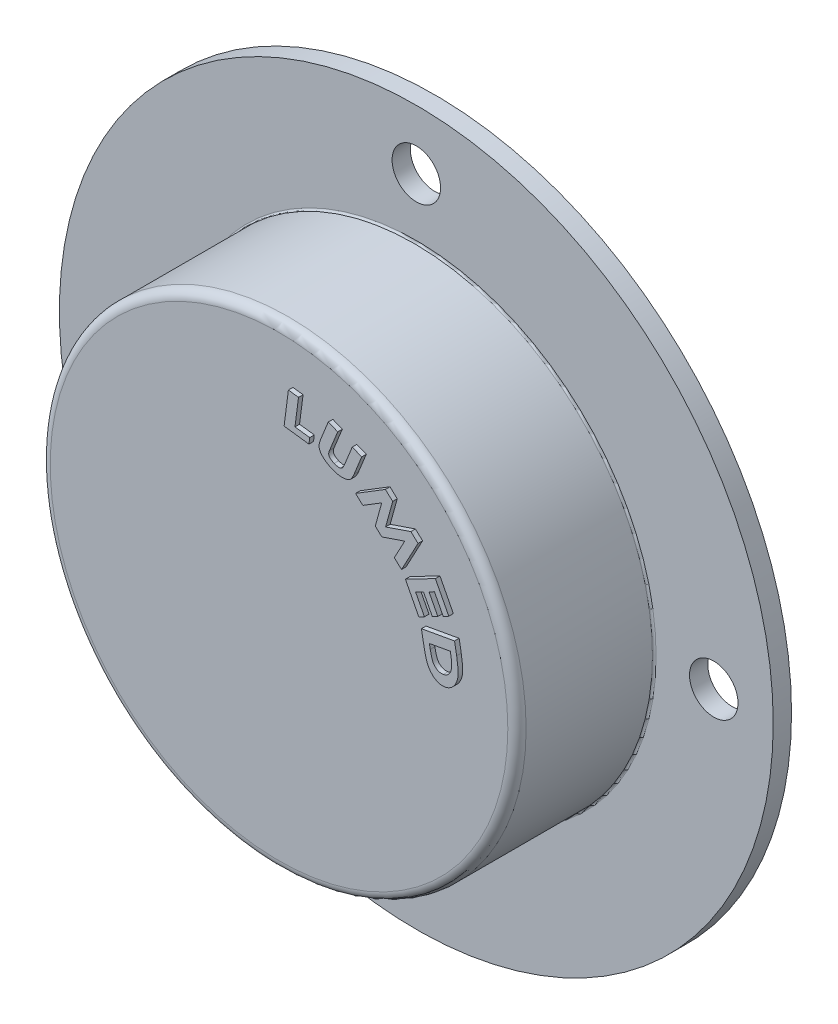
SolidWorks part; units mm, degrees
ref_plane "Front Plane" through (0, 0, 0) normal (0, 0, 1) x (1, 0, 0)
ref_plane "Top Plane" through (0, 0, 0) normal (0, 1, 0) x (1, 0, 0)
ref_plane "Right Plane" through (0, 0, 0) normal (1, 0, 0) x (0, 0, -1)
sketch "Sketch1" plane through (0, 0, 0) normal (0, 0, 1) x (1, 0, 0)
  circle A0 centre (0, 0) radius 39
  dimension "D1" = 78
extrude "Extrude1" add sketch "Sketch1" along normal blind 2
sketch "Sketch2" plane through (0, 0, 2) normal (0, 0, 1) x (1, 0, 0)
  circle A0 centre (0, 0) radius 26
  dimension "D1" = 52
extrude "Extrude3" add sketch "Sketch2" along normal blind 15
fillet "Fillet1" radius 1 1 edges at (26, 0, 17)
shell "Shell1" thickness 2 removed face at (39, 0, 0)
fillet "Fillet3" radius 0.2 1 edges at (26, 0, 2)
fillet "Fillet4" radius 0.5 1 edges at (24, 0, 0)
fillet "Fillet5" radius 1 1 edges at (24, 0, 15)
hole_wizard "M5 Clearance Hole2" positions "Sketch6" profile "Sketch5" hole size "M5" standard "Ansi Metric" end condition through all
sketch "Sketch6" plane through (0, 0, 2) normal (0, 0, 1) x (1, 0, 0)
  point P0 (0, 32.5)
  dimension "D1" = 32.5
sketch "Sketch5" plane through (0, 32.5, 2) normal (1, 0, 0) x (0, -1, 0)
  line L0 (0, 0) -> (0, 2)
  line L1 (0, 2) -> (2.65, 2)
  line L2 (2.65, 2) -> (2.65, 0)
  line L5 (2.65, 0) -> (0, 0)
  line L11 (0, -6.35) -> (0, 107.95) construction
  dimension "Thru Hole Dia." = 5.3
  dimension "Thru Hole Depth" = 2
pattern_circular "CirPattern2" count 4 over 360 about axis through (0, 0, 17) along (0, 0, -1) of "M5 Clearance Hole2"
sketch "Sketch7" plane through (0, 0, 17) normal (0, 0, 1) x (1, 0, 0)
  circle A0 centre (0, 0) radius 17 construction
  text T0 "<b>LUMED</b>" font "Century Gothic" height in points 14
  dimension "D1" = 34
extrude "Extrude4" add sketch "Sketch7" along normal blind 0.5
